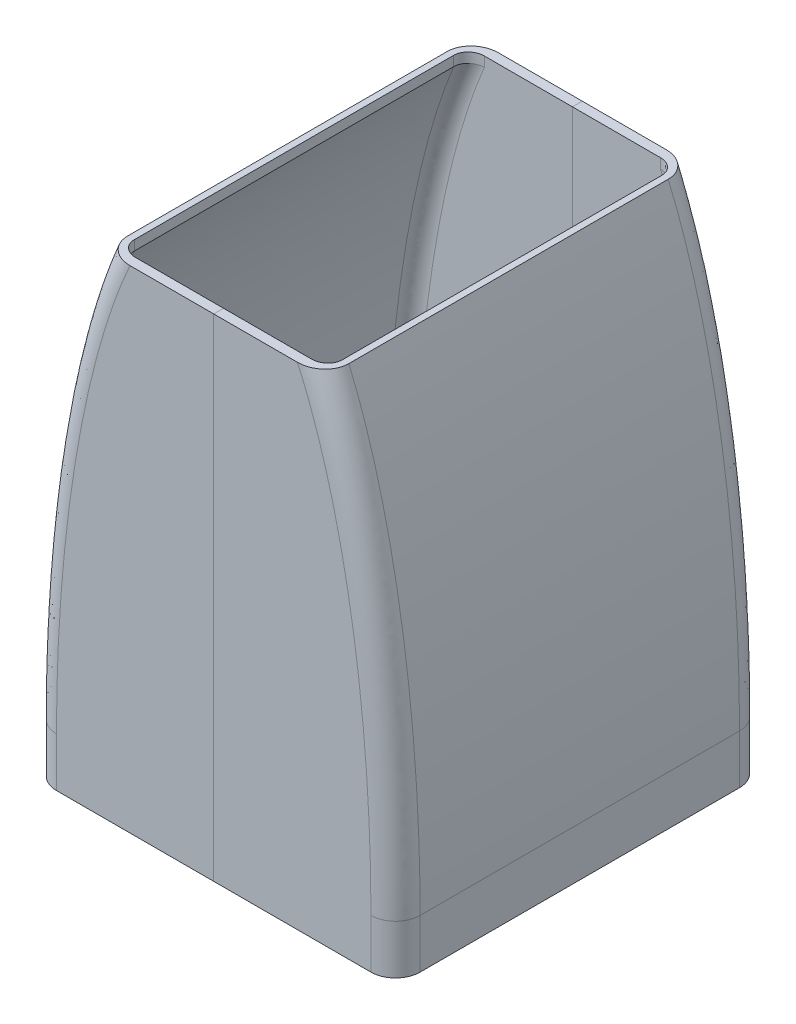
SolidWorks part; units mm, degrees
ref_plane "Front Plane" through (0, 0, 0) normal (0, 0, 1) x (1, 0, 0)
ref_plane "Top Plane" through (0, 0, 0) normal (0, 1, 0) x (1, 0, 0)
ref_plane "Right Plane" through (0, 0, 0) normal (1, 0, 0) x (0, 0, -1)
sketch "Sketch1" plane through (0, 0, 0) normal (0, 0, 1) x (1, 0, 0)
  line L0 (37, 0) -> (-37, 0)
  line L1 (-37, 0) -> (-37, 10)
  line L2 (-37, 10) -> (37, 10) construction
  line L3 (37, 10) -> (37, 0)
  line L4 (0, 0) -> (0, 100) construction
  line L5 (-22.5, 100) -> (22.5, 100)
  ellipse E0 centre (0, 10) end of major axis (0, -103.3709) minor radius 37 (-22.5, 100) -> (-37, 10) ccw
  ellipse E1 centre (0, 10) end of major axis (0, -103.3709) minor radius 37 (37, 10) -> (22.5, 100) ccw
  point P3 (0, 0)
  point P10 (0, 100)
  dimension "D1" = 74
  dimension "D2" = 10
  dimension "D3" = 45
  dimension "D4" = 100
extrude "Boss-Extrude1" add sketch "Sketch1" along normal blind 37.5 and the other way blind 37.5
fillet "Fillet1" radius 5 8 edges at (37, 5, 37.5) (33.1776, 60.1845, 37.5) (37, 5, -37.5) (33.1776, 60.1845, -37.5) (-37, 5, -37.5) (-33.1776, 60.1845, -37.5) (-37, 5, 37.5) (-33.1776, 60.1845, 37.5)
shell "Shell1" thickness 2 removed face at (0, 0, 0)
sketch "Sketch2" plane through (0, 98, 0) normal (0, -1, 0) x (1, 0, 0)
  line L8 (17.9172, 35.5) -> (-17.9172, 35.5)
  line L9 (-21.1687, 32.5) -> (-21.1687, -32.5)
  line L10 (-17.9172, -35.5) -> (17.9172, -35.5)
  line L11 (21.1687, -32.5) -> (21.1687, 32.5)
  line L12 (17.9172, 35.5) -> (-17.9172, 35.5)
  line L13 (-21.1687, 32.5) -> (-21.1687, -32.5)
  line L14 (-17.9172, -35.5) -> (17.9172, -35.5)
  line L15 (21.1687, -32.5) -> (21.1687, 32.5)
  spline S8 degree 3 poles (343.2926, -1931.0873) (92.9734, -333.9167) (11.0657, 40.653) (-18.7298, 35.4113) (-18.9303, 35.3576) (-19.314, 35.2167) (-19.4983, 35.1297) (-19.8509, 34.921) (-20.0185, 34.7992) (-20.3236, 34.5286) (-20.4637, 34.3778) (-20.7112, 34.0491) (-20.8165, 33.8745) (-20.9893, 33.5043) (-21.0568, 33.3072) (-25.7273, 12.4428) (203.8242, -48.7898) (1937.453, -370.5778) knots -18.24923 -18.24923 -18.24923 -18.24923 0.125 0.125 0.25 0.25 0.375 0.375 0.5 0.5 0.625 0.625 0.75 0.75 0.875 0.875 13.860896 13.860896 13.860896 13.860896 only from (-17.9172, 35.5) to (-21.1687, 32.5)
  spline S9 degree 3 poles (713.2757, -1891.1525) (62.1895, 22.8183) (-23.9951, -20.3068) (-21.0549, -33.3137) (-20.9886, -33.5062) (-20.8151, -33.877) (-20.707, -34.0552) (-20.4616, -34.38) (-20.3231, -34.5292) (-20.0154, -34.8017) (-19.848, -34.9228) (-19.4978, -35.1298) (-19.3135, -35.217) (7.1769, -44.9249) (109.9573, 275.2357) (-1885.2929, 631.6292) knots -7.887957 -7.887957 -7.887957 -7.887957 0.125 0.125 0.25 0.25 0.375 0.375 0.5 0.5 0.625 0.625 0.75 0.75 17.74891 17.74891 17.74891 17.74891 only from (-21.1687, -32.5) to (-17.9172, -35.5)
  spline S10 degree 3 poles (-343.2926, 1931.0873) (-92.9734, 333.9167) (-11.0657, -40.653) (18.7298, -35.4113) (18.9303, -35.3576) (19.314, -35.2167) (19.4983, -35.1297) (19.8509, -34.921) (20.0185, -34.7992) (20.3236, -34.5286) (20.4637, -34.3778) (20.7112, -34.0491) (20.8165, -33.8745) (20.9893, -33.5043) (21.0568, -33.3072) (25.7273, -12.4428) (-203.8242, 48.7898) (-1937.453, 370.5778) knots -18.24923 -18.24923 -18.24923 -18.24923 0.125 0.125 0.25 0.25 0.375 0.375 0.5 0.5 0.625 0.625 0.75 0.75 0.875 0.875 13.860896 13.860896 13.860896 13.860896 only from (17.9172, -35.5) to (21.1687, -32.5)
  spline S11 degree 3 poles (-713.2757, 1891.1525) (-62.1895, -22.8183) (23.9951, 20.3068) (21.0549, 33.3137) (20.9886, 33.5062) (20.8151, 33.877) (20.707, 34.0552) (20.4616, 34.38) (20.3231, 34.5292) (20.0154, 34.8017) (19.848, 34.9228) (19.4978, 35.1298) (19.3135, 35.217) (-7.1769, 44.9249) (-109.9573, -275.2357) (1885.2929, -631.6292) knots -7.887957 -7.887957 -7.887957 -7.887957 0.125 0.125 0.25 0.25 0.375 0.375 0.5 0.5 0.625 0.625 0.75 0.75 17.74891 17.74891 17.74891 17.74891 only from (21.1687, 32.5) to (17.9172, 35.5)
  spline S12 degree 3 poles (-17.9172, 35.5) (-18.1234, 35.5) (-18.3272, 35.4822) (-18.7298, 35.4113) (-18.9303, 35.3576) (-19.314, 35.2167) (-19.4983, 35.1297) (-19.8509, 34.921) (-20.0185, 34.7992) (-20.3236, 34.5286) (-20.4637, 34.3778) (-20.7112, 34.0491) (-20.8165, 33.8745) (-20.9893, 33.5043) (-21.0568, 33.3072) (-21.1459, 32.9093) (-21.1687, 32.7066) (-21.1687, 32.5) knots 0 0 0 0 0.125 0.125 0.25 0.25 0.375 0.375 0.5 0.5 0.625 0.625 0.75 0.75 0.875 0.875 1 1 1 1
  spline S13 degree 3 poles (-21.1687, -32.5) (-21.1687, -32.707) (-21.1452, -32.9142) (-21.0549, -33.3137) (-20.9886, -33.5062) (-20.8151, -33.877) (-20.707, -34.0552) (-20.4616, -34.38) (-20.3231, -34.5292) (-20.0154, -34.8017) (-19.848, -34.9228) (-19.4978, -35.1298) (-19.3135, -35.217) (-18.7334, -35.4296) (-18.3301, -35.5) (-17.9172, -35.5) knots 0 0 0 0 0.125 0.125 0.25 0.25 0.375 0.375 0.5 0.5 0.625 0.625 0.75 0.75 1 1 1 1
  spline S14 degree 3 poles (17.9172, -35.5) (18.1234, -35.5) (18.3272, -35.4822) (18.7298, -35.4113) (18.9303, -35.3576) (19.314, -35.2167) (19.4983, -35.1297) (19.8509, -34.921) (20.0185, -34.7992) (20.3236, -34.5286) (20.4637, -34.3778) (20.7112, -34.0491) (20.8165, -33.8745) (20.9893, -33.5043) (21.0568, -33.3072) (21.1459, -32.9093) (21.1687, -32.7066) (21.1687, -32.5) knots 0 0 0 0 0.125 0.125 0.25 0.25 0.375 0.375 0.5 0.5 0.625 0.625 0.75 0.75 0.875 0.875 1 1 1 1
  spline S15 degree 3 poles (21.1687, 32.5) (21.1687, 32.707) (21.1452, 32.9142) (21.0549, 33.3137) (20.9886, 33.5062) (20.8151, 33.877) (20.707, 34.0552) (20.4616, 34.38) (20.3231, 34.5292) (20.0154, 34.8017) (19.848, 34.9228) (19.4978, 35.1298) (19.3135, 35.217) (18.7334, 35.4296) (18.3301, 35.5) (17.9172, 35.5) knots 0 0 0 0 0.125 0.125 0.25 0.25 0.375 0.375 0.5 0.5 0.625 0.625 0.75 0.75 1 1 1 1
  dimension "D1" = 0
extrude "Cut-Extrude1" cut sketch "Sketch2" against normal up to next
split "Split1" trim tools "Right Plane" bodies to split 102 resulting bodies 103 104
